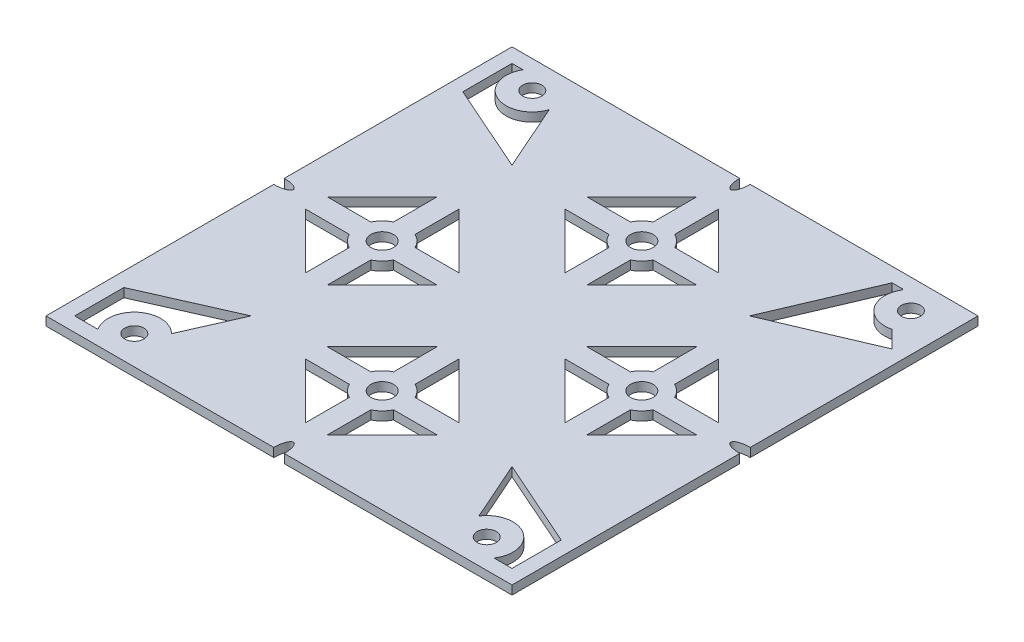
SolidWorks part; units mm, degrees
material "ABS"
ref_plane "Front Plane" through (0, 0, 0) normal (0, 0, 1) x (1, 0, 0)
ref_plane "Top Plane" through (0, 0, 0) normal (0, 1, 0) x (1, 0, 0)
ref_plane "Right Plane" through (0, 0, 0) normal (1, 0, 0) x (0, 0, -1)
sketch "Sketch1" plane through (0, 0, 0) normal (0, 1, 0) x (1, 0, 0)
  line L1 (0, 0) -> (97.6, 0)
  line L2 (0, 0) -> (0, 97.6)
  line L3 (0, 97.6) -> (97.6, 97.6)
  line L4 (97.6, 0) -> (97.6, 97.6)
  dimension "D1" = 97.6
  dimension "D2" = 97.6
extrude "Boss-Extrude1" add sketch "Sketch1" along normal blind 1.85
sketch "Sketch2" plane through (0, 0, 0) normal (0, -1, 0) x (-1, 0, 0)
  line L0 (-97.6, 97.6) -> (0, 0) construction
  line L1 (-97.6, 0) -> (0, 97.6) construction
  line L2 (-48.8, 97.6) -> (-48.8, 0) construction
  line L3 (-97.6, 97.6) -> (0, 97.6) construction
  line L4 (0, 0) -> (-97.6, 0) construction
  line L5 (-97.6, 48.8) -> (0, 48.8) construction
  line L6 (-97.6, 0) -> (-97.6, 97.6) construction
  line L7 (0, 97.6) -> (0, 0) construction
sketch "Sketch3" plane through (0, 0, 0) normal (0, -1, 0) x (1, 0, 0)
  line L0 (97.6, -97.6) -> (0, -97.6) construction
  line L1 (97.6, 0) -> (97.6, -97.6) construction
  line L2 (0, -97.6) -> (0, 0) construction
  line L3 (0, 0) -> (97.6, 0) construction
  line L4 (97.6, -94.6) -> (0, -94.6) construction
  line L5 (3, -97.6) -> (3, 0) construction
  line L6 (3, -94.6) -> (5.3161, -94.6)
  line L7 (3, -94.6) -> (3, -84.3)
  line L8 (3, -84.3) -> (21.4728, -76.1272)
  line L9 (97.6, 0) -> (0, -97.6) construction
  line L10 (21.4728, -76.1272) -> (13.3, -94.6)
  line L11 (21.4728, -21.4728) -> (13.3, -3)
  line L12 (3, -3) -> (13.3, -3)
  line L13 (0, -3) -> (97.6, -3) construction
  line L14 (3, -13.3) -> (3, -3)
  line L15 (3, -3) -> (7.8732, -3)
  line L16 (3, -13.3) -> (21.4728, -21.4728)
  line L17 (97.6, -97.6) -> (0, 0) construction
  line L18 (0, -97.6) -> (0, 0) construction
  line L19 (16.1614, -10.109) -> (21.4728, -21.4728) construction
  line L20 (94.6, -97.6) -> (94.6, 0) construction
  line L21 (94.6, -3) -> (94.6, -13.3)
  line L22 (94.6, -3) -> (84.3, -3)
  line L23 (94.6, -13.3) -> (76.1272, -21.4728)
  line L24 (76.1272, -21.4728) -> (84.3, -3)
  line L25 (94.6, -82.6) -> (73.6741, -73.6741)
  line L26 (73.6741, -73.6741) -> (82.6, -94.6)
  line L27 (94.6, -82.6) -> (82.6, -94.6) construction
  line L28 (94.6, -82.6) -> (91.0273, -86.1727)
  line L29 (82.6, -94.6) -> (85.1169, -94.6)
  line L30 (3, -94.6) -> (13.3, -94.6) construction
  circle A0 centre (89.66, -91.5) radius 1.25
  circle A1 centre (10.05, -91.8) radius 1.25
  circle A2 centre (12.45, -6.05) radius 1.25
  circle A3 centre (86.25, -6.05) radius 1.25
  circle A4 centre (89.66, -91.5) radius 5.5
  circle A5 centre (10.05, -91.8) radius 5.5
  circle A6 centre (12.45, -6.05) radius 5.5
  circle A7 centre (86.25, -6.05) radius 5.5
  dimension "D1" = 6.1
  dimension "D9" = 3
  dimension "D16" = 3
  dimension "D20" = 2.5
  dimension "D21" = 11
  dimension "D23" = 11
  dimension "D24" = 2.5
  dimension "D26" = 11
  dimension "D27" = 11
  dimension "D2" = 7.94
  dimension "D3" = 5.8
  dimension "D4" = 10.05
  dimension "D5" = 6.05
  dimension "D6" = 12.45
  dimension "D7" = 6.05
  dimension "D8" = 11.35
  dimension "D10" = 3
  dimension "D11" = 10.3
  dimension "D12" = 20.2
  dimension "D13" = 3
  dimension "D14" = 10.3
  dimension "D15" = 20.2
  dimension "D17" = 10.3
  dimension "D18" = 22.75
  dimension "D19" = 15
  dimension "D22" = 10.3
  dimension "D25" = 20.2
extrude "Cut-Extrude1" cut sketch "Sketch3" against normal blind 10 contours A2 | A1 | A1 | A5 L8 L7 L6 | A4 L28 L25 L26 L29 | A3 | A7 L24 L23 L21 L22 | A6 L15 L14 L16 | A0 region at (11.5662, 0, -84.2704) region at (10.6634, 0, -12.5774) region at (86.5986, 0, -12.9459) region at (83.266, 0, -83.1897) region at (10.05, 0, -91.8) region at (12.45, 0, -6.05) region at (86.25, 0, -6.05)
fillet "Fillet1" radius 0.2 1 edges at (85.1169, 0.925, -94.6)
sketch "Sketch5" plane through (0, 0, 0) normal (0, -1, 0) x (1, 0, 0)
  line L0 (78.0601, -69.3344) -> (24.4532, -15.7275) construction
  line L1 (15.9101, -24.6358) -> (67.2589, -75.9846) construction
  line L2 (97.6, -97.6) -> (0, 0) construction
  line L3 (25.594, -80.7317) -> (80.9701, -25.3556) construction
  line L4 (71.5743, -17.3) -> (16.8047, -72.0696) construction
  line L5 (97.6, 0) -> (0, -97.6) construction
  line L6 (51.05, -89.7671) -> (51.05, -80.6171)
  line L7 (46.55, -89.7671) -> (46.55, -80.6171)
  line L8 (48.8, -97.6) -> (48.8, 0) construction
  line L9 (51.05, -89.7671) -> (62.5825, -78.2346)
  line L10 (62.5825, -78.2346) -> (53.4325, -78.2346)
  line L11 (44.1675, -78.2346) -> (35.0175, -78.2346)
  line L12 (35.0175, -78.2346) -> (46.55, -89.7671)
  line L13 (48.8, -78.2346) -> (36.0473, -78.2346) construction
  line L14 (48.8, -73.7346) -> (36.0473, -73.7346) construction
  line L15 (44.1675, -73.7346) -> (35.0175, -73.7346)
  line L16 (46.55, -71.3521) -> (46.55, -62.2021)
  line L17 (53.4325, -73.7346) -> (62.5825, -73.7346)
  line L18 (51.05, -71.3521) -> (51.05, -62.2021)
  line L19 (62.5825, -73.7346) -> (51.05, -62.2021)
  line L20 (46.55, -62.2021) -> (35.0175, -73.7346)
  line L21 (48.8, -48.8) -> (-2.5605, -100.1605) construction
  line L22 (48.8, -48.8) -> (97.6, 0) construction
  line L23 (97.6, -97.6) -> (0, 0) construction
  line L24 (73.7346, -48.8) -> (73.7346, -36.0473) construction
  line L25 (78.2346, -48.8) -> (78.2346, -36.0473) construction
  line L26 (62.2021, -46.55) -> (73.7346, -35.0175)
  line L27 (73.7346, -62.5825) -> (62.2021, -51.05)
  line L28 (71.3521, -51.05) -> (62.2021, -51.05)
  line L29 (73.7346, -53.4325) -> (73.7346, -62.5825)
  line L30 (71.3521, -46.55) -> (62.2021, -46.55)
  line L31 (73.7346, -44.1675) -> (73.7346, -35.0175)
  line L32 (78.2346, -35.0175) -> (89.7671, -46.55)
  line L33 (78.2346, -44.1675) -> (78.2346, -35.0175)
  line L34 (78.2346, -62.5825) -> (78.2346, -53.4325)
  line L35 (89.7671, -51.05) -> (78.2346, -62.5825)
  line L36 (89.7671, -46.55) -> (80.6171, -46.55)
  line L37 (89.7671, -51.05) -> (80.6171, -51.05)
  line L38 (48.8, -19.3654) -> (61.5527, -19.3654) construction
  line L39 (48.8, -23.8654) -> (61.5527, -23.8654) construction
  line L40 (23.8654, -48.8) -> (23.8654, -61.5527) construction
  line L41 (19.3654, -48.8) -> (19.3654, -61.5527) construction
  line L42 (46.55, -7.8329) -> (46.55, -16.9829)
  line L43 (51.05, -7.8329) -> (51.05, -16.9829)
  line L44 (46.55, -7.8329) -> (35.0175, -19.3654)
  line L45 (35.0175, -19.3654) -> (44.1675, -19.3654)
  line L46 (53.4325, -19.3654) -> (62.5825, -19.3654)
  line L47 (62.5825, -19.3654) -> (51.05, -7.8329)
  line L48 (53.4325, -23.8654) -> (62.5825, -23.8654)
  line L49 (51.05, -26.2479) -> (51.05, -35.3979)
  line L50 (44.1675, -23.8654) -> (35.0175, -23.8654)
  line L51 (46.55, -26.2479) -> (46.55, -35.3979)
  line L52 (35.0175, -23.8654) -> (46.55, -35.3979)
  line L53 (51.05, -35.3979) -> (62.5825, -23.8654)
  line L54 (35.3979, -51.05) -> (23.8654, -62.5825)
  line L55 (23.8654, -35.0175) -> (35.3979, -46.55)
  line L56 (26.2479, -46.55) -> (35.3979, -46.55)
  line L57 (23.8654, -44.1675) -> (23.8654, -35.0175)
  line L58 (26.2479, -51.05) -> (35.3979, -51.05)
  line L59 (23.8654, -53.4325) -> (23.8654, -62.5825)
  line L60 (19.3654, -62.5825) -> (7.8329, -51.05)
  line L61 (19.3654, -53.4325) -> (19.3654, -62.5825)
  line L62 (19.3654, -35.0175) -> (19.3654, -44.1675)
  line L63 (7.8329, -46.55) -> (19.3654, -35.0175)
  line L64 (7.8329, -51.05) -> (16.9829, -51.05)
  line L65 (7.8329, -46.55) -> (16.9829, -46.55)
  line L66 (49.9, -97.6) -> (47.7, -97.6)
  line L67 (97.6, -97.6) -> (0, -97.6) construction
  line L68 (97.6, -48.8) -> (97.6, -49.9)
  line L69 (97.6, 0) -> (97.6, -97.6) construction
  line L70 (97.6, -48.8) -> (97.6, -47.7)
  line L71 (0, -49.9) -> (0, -48.8)
  line L72 (0, -97.6) -> (0, 0) construction
  line L73 (0, -48.8) -> (0, -47.7)
  line L74 (48.8, 0) -> (49.9, 0)
  line L75 (0, 0) -> (97.6, 0) construction
  line L76 (48.8, 0) -> (47.7, 0)
  circle A0 centre (48.8, -75.9846) radius 2.375
  circle A1 centre (48.8, -75.9846) radius 5.15
  circle A2 centre (75.9846, -48.8) radius 5.15
  circle A3 centre (75.9846, -48.8) radius 2.375
  circle A4 centre (48.8, -21.6154) radius 2.375
  circle A5 centre (48.8, -21.6154) radius 5.15
  circle A6 centre (21.6154, -48.8) radius 5.15
  circle A7 centre (21.6154, -48.8) radius 2.375
  ellipse E0 centre (48.8, -97.6) end of major axis (48.8, -94.6046) minor radius 1.1
  ellipse E1 centre (97.6, -48.8) end of major axis (94.5962, -48.8) minor radius 1.1
  ellipse E2 centre (0, -48.8) end of major axis (3, -48.8) minor radius 1.1
  ellipse E3 centre (48.8, 0) end of major axis (48.8, -3) minor radius 1.1
  line M15 (0, 0) -> (0, -97.6)
  line M16 (0, -97.6) -> (97.6, -97.6)
  line M17 (97.6, -97.6) -> (97.6, 0)
  line M18 (97.6, 0) -> (0, 0)
  dimension "D5" = 9.15
  dimension "D7" = 4.75
  dimension "D8" = 10.3
  dimension "D1" = 6.17
  dimension "D2" = 6.17
  dimension "D3" = 6.17
  dimension "D4" = 6.17
  dimension "D6" = 2.25
  dimension "D9" = 2.25
  dimension "D10" = 1.1
  dimension "D11" = 1.1
  dimension "D12" = 1.1
  dimension "D13" = 3
  dimension "D14" = 2.25
  dimension "D15" = 2.25
  dimension "D16" = 3
extrude "Cut-Extrude2" cut sketch "Sketch5" against normal blind 10 contours A1 L6 L9 L10 | A1 L11 L12 L7 | A0 | A1 L17 L19 L18 | A1 L16 L20 L15 | L61 A6 L64 L60 | L58 A6 L59 L54 | L57 A6 L56 L55 | L65 A6 L62 L63 | A7 | A3 | L37 A2 L34 L35 | L29 A2 L28 L27 | L30 A2 L31 L26 | L33 A2 L36 L32 | A5 L42 L44 L45 | A5 L46 L47 L43 | A5 L49 L53 L48 | A5 L50 L52 L51 | E0 M16 | E3 M18 | E1 M17 | E2 M15 | A4 region at (55.0576, 0, -82.2422) region at (42.5424, 0, -82.2422) region at (42.5424, 0, -69.7269) region at (55.0576, 0, -69.7269) region at (69.7269, 0, -42.5424) region at (69.7269, 0, -55.0576) region at (82.2422, 0, -42.5424) region at (82.2422, 0, -55.0576) region at (42.5424, 0, -15.3578) region at (55.0576, 0, -15.3578) region at (42.5424, 0, -27.8731) region at (55.0576, 0, -27.8731) region at (27.8731, 0, -55.0576) region at (15.3578, 0, -55.0576) region at (27.8731, 0, -42.5424) region at (15.3578, 0, -42.5424) region at (48.8, 0, -96.3287) region at (96.3251, 0, -48.8) region at (1.2732, 0, -48.8) region at (48.8, 0, -1.2732) region at (48.8, 0, -75.9846) region at (75.9846, 0, -48.8) region at (21.6154, 0, -48.8)
sketch "Sketch6" plane through (0, 0, 0) normal (0, -1, 0) x (1, 0, 0)
  circle A0 centre (12.45, -6.05) radius 2
  circle A1 centre (86.25, -6.05) radius 2
  circle A2 centre (10.05, -91.8) radius 2
  circle A3 centre (89.66, -91.5) radius 2
  dimension "D1" = 4
  dimension "D2" = 4
  dimension "D3" = 4
  dimension "D4" = 4
extrude "Cut-Extrude3" cut sketch "Sketch6" against normal through all
